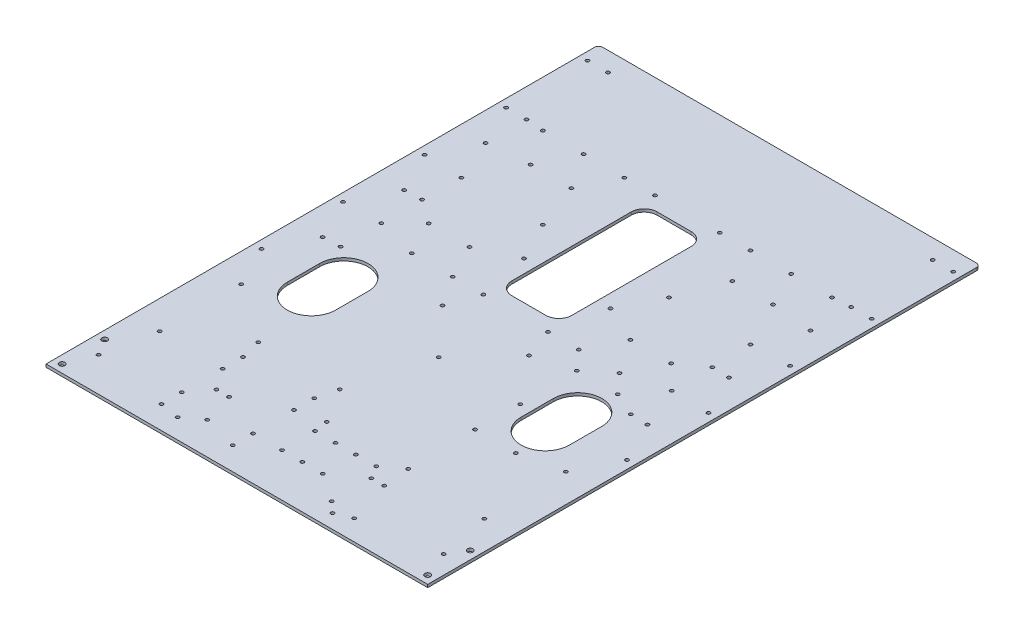
SolidWorks part; units mm, degrees
material "5052-H38"
ref_plane "Front" through (0, 0, 0) normal (0, 0, 1) x (1, 0, 0)
ref_plane "Top" through (0, 0, 0) normal (0, 1, 0) x (1, 0, 0)
ref_plane "Right" through (0, 0, 0) normal (1, 0, 0) x (0, 0, -1)
ref_axis "side-side" through (80.9, 0, 0) along (-1, 0, 0)
ref_axis "up-down" through (0, 50, 0) along (0, -1, 0)
ref_axis "front-back" through (0, 0, -80.9) along (0, 0, 1)
sketch "Sketch1" plane through (0, 0, 0) normal (0, 1, 0) x (1, 0, 0)
  line L1 (-149.877, 222.25) -> (149.877, 222.25)
  line L2 (-149.877, 222.25) -> (-149.877, -213.36)
  line L3 (-149.877, -213.36) -> (149.877, -213.36)
  line L4 (149.877, 222.25) -> (149.877, -213.36)
  line L5 (0, 222.25) -> (0, 171.3955) construction
  line L6 (0, -50) -> (0, 50) construction
  line L8 (-50, 0) -> (50, 0) construction
  dimension "D1" = 149.877
  dimension "D2" = 213.36
  dimension "D3" = 222.25
extrude "Boss-Extrude1" add sketch "Sketch1" along normal blind 2.286
sketch "Sketch3" plane through (0, 0, 0) normal (0, -1, 0) x (1, 0, 0)
  line L0 (-149.877, 213.36) -> (149.877, 213.36) construction
  line L1 (133.35, 213.36) -> (-133.35, 213.36)
  line L2 (133.35, 213.36) -> (133.35, 211.074)
  line L3 (133.35, 211.074) -> (-133.35, 211.074)
  line L4 (-133.35, 213.36) -> (-133.35, 211.074)
  line L5 (0, -50) -> (0, 50) construction
  point P6 (0, 213.36)
  dimension "D1" = 2.286
  dimension "D2" = 266.7
extrude "Boss-Extrude2" add sketch "Sketch3" against normal blind 15.24
fillet "Fillet1" radius 5.08 2 edges at (-133.35, 15.24, 212.217) (133.35, 15.24, 212.217)
sketch "Sketch4" plane through (0, 0, 0) normal (0, 1, 0) x (1, 0, 0)
  line L1 (133.35, -213.36) -> (133.35, -211.074) construction
  line L2 (119.528, 227.33) -> (119.528, 190.5)
  line L3 (-23.524, 131.65) -> (23.524, 131.65)
  line L4 (-119.528, 190.5) -> (-67.597, 190.5)
  line L5 (-50, 0) -> (50, 0) construction
  line L6 (149.877, 222.25) -> (-149.877, 222.25) construction
  line L7 (-67.597, 146.05) -> (-67.597, 190.5)
  line L8 (-67.597, 146.05) -> (67.597, 146.05)
  line L10 (67.597, 146.05) -> (67.597, 190.5)
  line L12 (67.597, 190.5) -> (119.528, 190.5)
  line L13 (-119.528, 227.33) -> (119.528, 227.33)
  line L14 (149.877, 222.25) -> (-149.877, 222.25) construction
  line L15 (-91.803, -61.3583) -> (-91.803, -35.9583) construction
  line L16 (-110.803, -61.3583) -> (-110.803, -35.9583)
  line L17 (-72.803, -61.3583) -> (-72.803, -35.9583)
  line L18 (0, -338.0059) -> (0, 0) construction
  line L19 (0, -50) -> (0, 50) construction
  line L20 (91.803, -61.3583) -> (91.803, -35.9583) construction
  line L21 (110.803, -61.3583) -> (110.803, -35.9583)
  line L22 (72.803, -61.3583) -> (72.803, -35.9583)
  line L23 (-119.528, 227.33) -> (-119.528, 190.5)
  line L24 (-49.276, -48.6583) -> (-49.276, -212.8608) construction
  line L26 (-23.524, 131.65) -> (-23.524, 17.586)
  line L27 (149.877, -213.36) -> (133.35, -213.36)
  line L28 (23.524, 131.65) -> (23.524, 17.586)
  line L29 (149.877, -213.36) -> (149.877, -211.7593)
  line L30 (-23.524, 17.586) -> (23.524, 17.586)
  line L31 (149.877, -211.7593) -> (134.874, -211.7593)
  line L32 (133.35, -213.36) -> (133.35, -209.55)
  line L33 (133.35, -211.074) -> (-133.35, -211.074) construction
  line L34 (-149.877, -213.36) -> (-133.35, -213.36)
  line L35 (-149.877, -213.36) -> (-149.877, -211.7593)
  line L36 (133.35, -209.55) -> (134.874, -209.55)
  line L37 (134.874, -211.7593) -> (134.874, -209.55)
  line L38 (-149.877, -211.7593) -> (-134.874, -211.7593)
  line L39 (-133.35, -209.55) -> (-134.874, -209.55)
  line L40 (-134.874, -211.7593) -> (-134.874, -209.55)
  line L41 (-133.35, -213.36) -> (-133.35, -209.55)
  line L43 (1.4, -177.7103) -> (33.4, -177.7103) construction
  line L44 (25.4, -168.8375) -> (25.4, -202.872) construction
  arc A0 (-110.803, -61.3583) -> (-72.803, -61.3583) centre (-91.803, -61.3583) ccw
  arc A1 (-72.803, -35.9583) -> (-110.803, -35.9583) centre (-91.803, -35.9583) ccw
  arc A3 (110.803, -61.3583) -> (72.803, -61.3583) centre (91.803, -61.3583) cw
  arc A4 (72.803, -35.9583) -> (110.803, -35.9583) centre (91.803, -35.9583) cw
  circle A5 centre (143.527, -205.4093) radius 2.2225
  circle A7 centre (143.527, -172.0083) radius 2.2225
  circle A9 centre (127.528, -144.8583) radius 1.3525
  circle A10 centre (127.528, -80.8583) radius 1.3526
  circle A11 centre (127.528, -16.8583) radius 1.3526
  circle A12 centre (127.528, 47.1417) radius 1.3526
  circle A13 centre (127.528, 111.1417) radius 1.3526
  circle A14 centre (143.528, 79.1417) radius 1.3526
  circle A15 centre (143.528, 143.1417) radius 1.3525
  circle A16 centre (143.528, 207.1417) radius 1.3525
  circle A17 centre (127.528, 207.1417) radius 1.3525
  circle A18 centre (127.528, 143.1417) radius 1.3525
  circle A19 centre (143.528, 15.1417) radius 1.3526
  circle A20 centre (143.528, -48.8583) radius 1.3526
  circle A21 centre (-143.528, -48.8583) radius 1.3526
  circle A22 centre (-143.528, 15.1417) radius 1.3526
  circle A23 centre (-127.528, 143.1417) radius 1.3525
  circle A24 centre (-127.528, 207.1417) radius 1.3525
  circle A25 centre (-143.528, 207.1417) radius 1.3525
  circle A26 centre (-143.528, 143.1417) radius 1.3525
  circle A27 centre (-143.528, 79.1417) radius 1.3526
  circle A28 centre (-127.528, 111.1417) radius 1.3526
  circle A29 centre (-127.528, 47.1417) radius 1.3526
  circle A30 centre (-127.528, -16.8583) radius 1.3526
  circle A31 centre (-127.528, -80.8583) radius 1.3526
  circle A32 centre (-127.528, -144.8583) radius 1.3525
  circle A33 centre (-143.527, -172.0083) radius 2.2225
  circle A34 centre (-143.527, -205.4093) radius 2.2225
  circle A35 centre (-21.276, -193.7103) radius 1.3526
  circle A36 centre (-21.276, -177.7103) radius 1.3526
  circle A37 centre (-21.276, -145.7103) radius 1.3526
  circle A38 centre (-21.276, -129.7103) radius 1.3526
  circle A39 centre (-17.276, -113.7103) radius 1.3526
  circle A40 centre (-81.276, -113.7103) radius 1.3526
  circle A41 centre (-77.276, -129.7103) radius 1.3526
  circle A42 centre (-77.276, -145.7103) radius 1.3526
  circle A43 centre (-77.276, -177.7103) radius 1.3526
  circle A44 centre (-77.276, -193.7103) radius 1.3526
  circle A45 centre (-114.003, 47.68) radius 1.3525
  circle A47 centre (-114.003, -16.32) radius 1.3525
  circle A48 centre (-114.003, 15.68) radius 1.3525
  circle A49 centre (-34.003, 47.68) radius 1.3526
  circle A50 centre (-34.003, 15.68) radius 1.3525 construction
  circle A51 centre (-34.003, -16.32) radius 1.3525
  circle A52 centre (114.004, 47.68) radius 1.3526
  circle A53 centre (114.004, 15.68) radius 1.3525
  circle A54 centre (114.004, -16.32) radius 1.3525
  circle A55 centre (34.004, -16.32) radius 1.3525
  circle A56 centre (34.004, 15.68) radius 1.3525 construction
  circle A57 centre (34.004, 47.68) radius 1.3526
  circle A58 centre (113.504, 78.05) radius 1.3526
  circle A59 centre (49.504, 78.05) radius 1.3526
  circle A60 centre (49.504, 142.05) radius 1.3525
  circle A61 centre (113.504, 142.05) radius 1.3525
  circle A62 centre (-113.503, 78.05) radius 1.3526
  circle A63 centre (-113.503, 142.05) radius 1.3526
  circle A64 centre (-49.503, 142.05) radius 1.3525
  circle A65 centre (-49.503, 78.05) radius 1.3526
  circle A66 centre (-55.63, -179.4842) radius 2.8702 construction
  circle A67 centre (-0.276, -52.9198) radius 1.3526
  circle A68 centre (63.7245, -52.9198) radius 1.3525
  circle A69 centre (-0.276, -140.92) radius 1.3525
  circle A70 centre (63.7245, -140.92) radius 1.3525
  circle A71 centre (-25.4, 7.186) radius 1.3526
  circle A73 centre (25.4, 7.186) radius 1.3526
  circle A75 centre (-81.504, 7.186) radius 1.3525
  circle A76 centre (-49.504, 7.186) radius 1.3526
  circle A77 centre (49.503, 7.186) radius 1.3526
  circle A78 centre (81.503, 7.186) radius 1.3525
  circle A81 centre (-62.63, -186.4842) radius 2.8702 construction
  circle A82 centre (-62, -196.2342) radius 2.8702 construction
  circle A83 centre (-55.63, -162.2342) radius 1.3525
  circle A84 centre (-65.63, -162.2342) radius 1.3525
  circle A85 centre (-62, -196.2342) radius 1.3525
  circle A86 centre (-48.63, -186.4842) radius 1.3525
  circle A87 centre (55.63, -161.7342) radius 1.3525
  circle A88 centre (65.63, -161.7342) radius 1.3525
  circle A89 centre (64.0503, -200.684) radius 1.3525
  circle A90 centre (76, -195.7342) radius 1.3525
  circle A91 centre (55.63, -192.9842) radius 1.3525
  circle A92 centre (135.528, -184.8583) radius 1.3525
  circle A93 centre (-135.527, -184.8583) radius 1.3525
  circle A94 centre (63.18, -87.8714) radius 1.3526
  circle A95 centre (95.18, -87.8714) radius 1.3526
  circle A96 centre (63.18, -7.8714) radius 1.3525
  circle A97 centre (95.18, -7.8714) radius 1.3525
  circle A98 centre (63.18, 34.1) radius 1.3525
  circle A99 centre (95.18, 34.1) radius 1.3525
  circle A100 centre (63.18, 114.1) radius 1.3526
  circle A101 centre (95.18, 114.1) radius 1.3526
  circle A102 centre (-95.18, 34.1) radius 1.3525
  circle A103 centre (-63.18, 34.1) radius 1.3526
  circle A104 centre (-95.18, 114.1) radius 1.3526
  circle A105 centre (-63.18, 114.1) radius 1.3526
  circle A106 centre (-81.503, 142.05) radius 1.3525
  circle A107 centre (-25.4, 142.05) radius 1.3525
  circle A108 centre (25.4, 142.05) radius 1.3525
  circle A109 centre (81.504, 142.05) radius 1.3525
  circle A110 centre (1.4, -177.7103) radius 1.3525
  circle A111 centre (17.4, -177.7103) radius 1.3525
  circle A112 centre (33.4, -177.7103) radius 1.3525
  circle A113 centre (33.4, -177.7103) radius 4.3688 construction
  circle A114 centre (1.4, -177.7103) radius 4.3688 construction
  circle A115 centre (1.4, -151.7103) radius 1.3525
  circle A116 centre (33.4, -151.7103) radius 1.3525
  circle A117 centre (17.4, -151.7103) radius 1.3525
  circle A118 centre (49.4, -151.7103) radius 1.3525
  point P24 (-91.803, -48.6583)
  point P40 (91.803, -48.6583)
  dimension "D8" = 4.445
  dimension "D9" = 2.7051
  dimension "D10" = 2.7051
  dimension "D13" = 5.7404
  dimension "D14" = 2.7051
  dimension "D15" = 2.7051
  dimension "D16" = 2.7051
  dimension "D17" = 2.7051
  dimension "D18" = 2.7051
  dimension "D19" = 2.7051
  dimension "D20" = 2.7051
  dimension "D23" = 2.7051
  dimension "D24" = 2.7051
  dimension "D25" = 2.7051
  dimension "D26" = 2.7051
  dimension "D27" = 2.7051
  dimension "D28" = 2.7051
  dimension "D29" = 2.7051
  dimension "D30" = 2.7051
  dimension "D31" = 2.7051
  dimension "D32" = 2.7051
  dimension "D33" = 2.7051
  dimension "D34" = 2.7051
  dimension "D35" = 2.7051
  dimension "D36" = 2.7051
  dimension "D37" = 2.7051
  dimension "D38" = 8.7376
  dimension "D39" = 2.7051
  dimension "D45" = 16
  dimension "D1" = 190.5
  dimension "D2" = 76.2
  dimension "D5" = 5.08
  dimension "D6" = 38
  dimension "D7" = 25.4
  dimension "D21" = 1.524
  dimension "D22" = 1.524
  dimension "D40" = 1.4
  dimension "D42" = 32
  dimension "D43" = 8
  dimension "D44" = 26
extrude "Cut-Extrude1" cut sketch "Sketch4" along normal blind 7.62
fillet "Fillet2" radius 3.175 4 edges at (149.877, 1.143, -222.25) (119.528, 1.143, -222.25) (-149.877, 1.143, -222.25) (-119.528, 1.143, -222.25)
fillet "Fillet3" radius 5.842 6 edges at (67.597, 1.143, -190.5) (-67.597, 1.143, -190.5) (119.528, 1.143, -190.5) (67.597, 1.143, -146.05) (-67.597, 1.143, -146.05) (-119.528, 1.143, -190.5)
fillet "Fillet4" radius 10.16 4 edges at (23.524, 1.143, -17.586) (-23.524, 1.143, -17.586) (23.524, 1.143, -131.65) (-23.524, 1.143, -131.65)
other "DeleteFace1" face at (0, 9.5794, 211.074) face at (131.3361, 13.2261, 212.217) face at (0, 15.24, 212.217) face at (133.35, 4.1487, 211.328) face at (0, 8.8174, 213.36) face at (134.112, 1.143, 209.55) face at (134.874, 1.143, 210.6546) face at (-131.3361, 13.2261, 212.217) face at (-133.35, 4.1487, 211.328) face at (-134.112, 1.143, 209.55) face at (-134.874, 1.143, 210.6546) face at (-142.3755, 1.143, 211.7593) and patch yes
sketch "Sketch5" plane through (0, 2.286, 0) normal (0, 1, 0) x (1, 0, 0)
  line L0 (61.755, 146.05) -> (-61.755, 146.05) construction
  line L1 (122.703, 222.25) -> (-122.703, 222.25)
  line L2 (122.703, 222.25) -> (122.703, 146.05)
  line L3 (122.703, 146.05) -> (-122.703, 146.05)
  line L4 (-122.703, 222.25) -> (-122.703, 146.05)
extrude "Boss-Extrude3" add sketch "Sketch5" against normal up to surface (2.286 mm away) up to face at (0, 0, -157.358)
